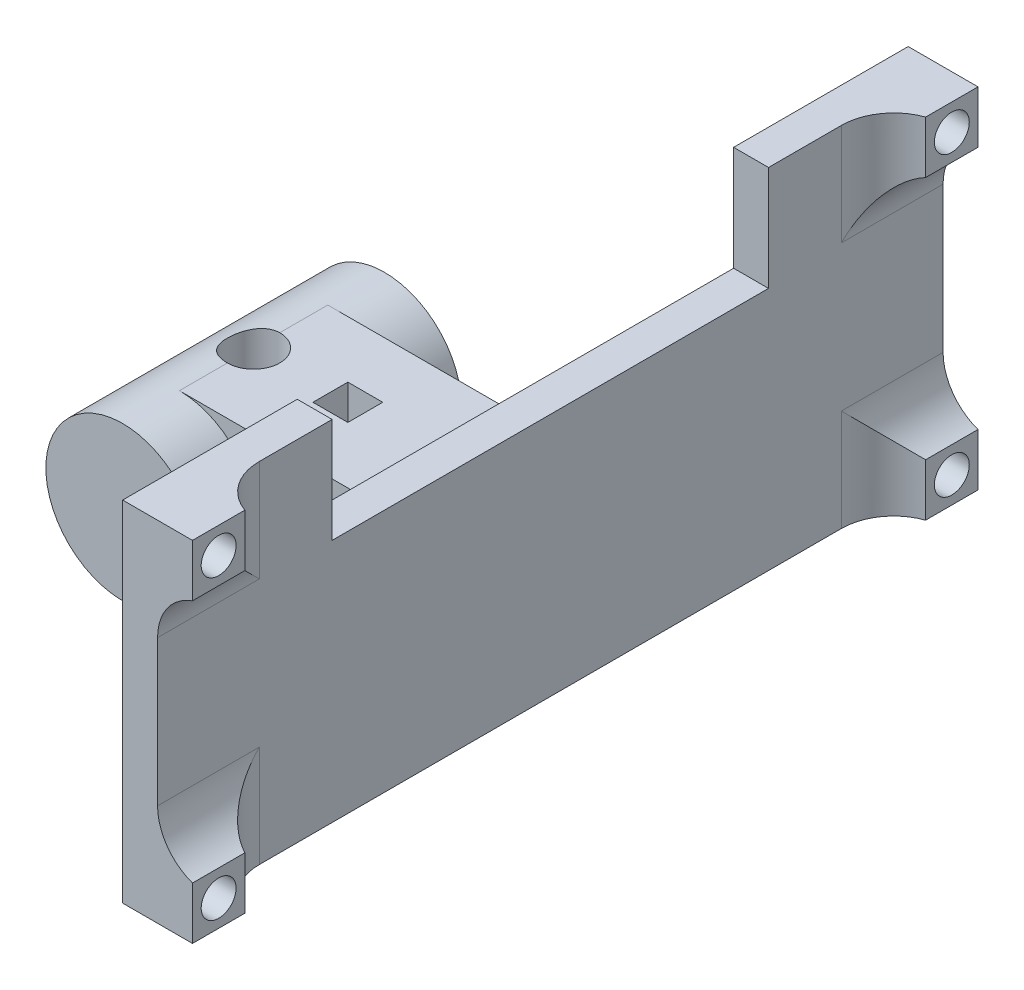
SolidWorks part; units mm, degrees
ref_plane "Front Plane" through (0, 0, 0) normal (0, 0, 1) x (1, 0, 0)
ref_plane "Top Plane" through (0, 0, 0) normal (0, 1, 0) x (1, 0, 0)
ref_plane "Right Plane" through (0, 0, 0) normal (1, 0, 0) x (0, 0, -1)
sketch "Sketch1" plane through (0, 0, 0) normal (0, 0, 1) x (1, 0, 0)
  circle A0 centre (0, 0) radius 4.4
  dimension "D1" = 8.8
extrude "Boss-Extrude1" add sketch "Sketch1" along normal mid plane 15
sketch "Sketch2" plane through (0, 0, 0) normal (1, 0, 0) x (0, 0, -1)
  line L0 (7.5, 4.4) -> (-7.5, 4.4) construction
  line L1 (7.5, 4.4) -> (-7.5, 4.4) construction
  line L3 (-4.25, -4.4) -> (4.25, -4.4)
  line L4 (-4.25, -4.4) -> (-4.25, 4.4)
  line L5 (-4.25, 4.4) -> (4.25, 4.4)
  line L6 (4.25, -4.4) -> (4.25, 4.4)
  line L7 (-4.25, -4.4) -> (4.25, 4.4) construction
  line L8 (-4.25, 4.4) -> (4.25, -4.4) construction
  point P0 (0, 0)
  dimension "D1" = 8.5
extrude "Boss-Extrude2" add sketch "Sketch2" along normal blind 15
sketch "Sketch3" plane through (15, 0, 0) normal (1, 0, 0) x (0, 0, -1)
  line L0 (-4.25, -4.4) -> (4.25, -4.4) construction
  line L1 (-22.5, -4.4) -> (22.5, -4.4)
  line L2 (-22.5, -4.4) -> (-22.5, 15.6)
  line L3 (-22.5, 15.6) -> (22.5, 15.6)
  line L4 (22.5, -4.4) -> (22.5, 15.6)
  point P6 (0, 15.6)
  dimension "D1" = 45
  dimension "D2" = 20
extrude "Boss-Extrude3" add sketch "Sketch3" along normal blind 4
sketch "Sketch4" plane through (19, 0, 0) normal (1, 0, 0) x (0, 0, -1)
  line L0 (-22.5, 5.6) -> (22.5, 5.6) construction
  line L1 (-22.5, 15.6) -> (-22.5, -4.4) construction
  line L2 (22.5, -4.4) -> (22.5, 15.6) construction
  line L3 (0, 15.6) -> (0, -4.4) construction
  line L4 (22.5, 15.6) -> (-22.5, 15.6) construction
  line L5 (-22.5, -4.4) -> (22.5, -4.4) construction
  circle A0 centre (-21, 14.1) radius 1
  circle A1 centre (-21, -2.9) radius 1
  circle A2 centre (21, -2.9) radius 1
  circle A3 centre (21, 14.1) radius 1
  dimension "D1" = 2
  dimension "D2" = 17
  dimension "D3" = 42
extrude "Cut-Extrude1" cut sketch "Sketch4" against normal through all
sketch "Sketch5" plane through (19, 0, 0) normal (1, 0, 0) x (0, 0, -1)
  line L0 (-19.5, 15.6) -> (19.5, 15.6)
  line L1 (-22.5, 15.6) -> (-19.5, 15.6)
  line L2 (-22.5, 15.6) -> (-22.5, 12.6)
  line L3 (-22.5, 12.6) -> (-19.5, 12.6)
  line L4 (-19.5, 15.6) -> (-19.5, 12.6)
  line L5 (-22.5, -4.4) -> (-19.5, -4.4)
  line L6 (-22.5, -4.4) -> (-22.5, -1.4)
  line L7 (-22.5, -1.4) -> (-19.5, -1.4)
  line L8 (-19.5, -4.4) -> (-19.5, -1.4)
  line L9 (22.5, -4.4) -> (19.5, -4.4)
  line L10 (22.5, -4.4) -> (22.5, -1.4)
  line L11 (22.5, -1.4) -> (19.5, -1.4)
  line L12 (19.5, -4.4) -> (19.5, -1.4)
  line L13 (22.5, 15.6) -> (19.5, 15.6)
  line L14 (22.5, 15.6) -> (22.5, 12.6)
  line L15 (22.5, 12.6) -> (19.5, 12.6)
  line L16 (19.5, 15.6) -> (19.5, 12.6)
  line L17 (22.5, 12.6) -> (22.5, -1.4)
  line L18 (19.5, -4.4) -> (-19.5, -4.4)
  line L19 (-22.5, -1.4) -> (-22.5, 12.6)
  line M19 (-22.5, 15.6) -> (-22.5, -4.4)
  line M20 (-22.5, -4.4) -> (22.5, -4.4)
  line M21 (22.5, -4.4) -> (22.5, 15.6)
  line M22 (22.5, 15.6) -> (-22.5, 15.6)
  dimension "D1" = 3
extrude "Cut-Extrude2" cut sketch "Sketch5" against normal blind 2 contours L16 L4 L3 L7 L8 L12 L11 L15 M22 M19 M20 M21 region at (19, 5.6, 0)
sketch "Sketch6" plane through (17, 0, 0) normal (1, 0, 0) x (0, 0, -1)
  line L0 (19.5, 15.6) -> (-19.5, 15.6) construction
  line L1 (-12.5, 15.6) -> (12.5, 15.6)
  line L2 (-12.5, 15.6) -> (-12.5, 9.6)
  line L3 (-12.5, 9.6) -> (12.5, 9.6)
  line L4 (12.5, 15.6) -> (12.5, 9.6)
  point P6 (0, 9.6)
  dimension "D1" = 25
  dimension "D2" = 6
extrude "Cut-Extrude3" cut sketch "Sketch6" against normal blind 2
sketch "Sketch7" plane through (0, 4.4, 0) normal (0, 1, 0) x (1, 0, 0)
  circle A0 centre (0, 0) radius 1.5
  dimension "D1" = 3
extrude "Cut-Extrude4" cut sketch "Sketch7" against normal through all both and the other way through all
ref_plane "Plane1" through (0, 0, 0) normal (0, 1, 0) x (1, 0, 0)
sketch "Sketch8" plane through (0, 0, 0) normal (0, 1, 0) x (1, 0, 0)
  line L0 (4.4, 4.25) -> (4.4, 7.5) construction
  line L1 (4.4, 1) -> (6.4, 1)
  line L2 (4.4, 1) -> (4.4, -1)
  line L3 (4.4, -1) -> (6.4, -1)
  line L4 (6.4, 1) -> (6.4, -1)
  point P6 (6.6781, 1.9482)
  point P7 (4.4, 0)
  dimension "D1" = 2
  dimension "D2" = 2
extrude "Cut-Extrude5" cut sketch "Sketch8" against normal through all both and the other way through all
fillet "Fillet1" radius 3 8 edges at (17, -1.4, -21) (17, -2.9, -19.5) (17, 14.1, -19.5) (17, 12.6, -21) (17, -2.9, 19.5) (17, -1.4, 21) (17, 14.1, 19.5) (17, 12.6, 21)
